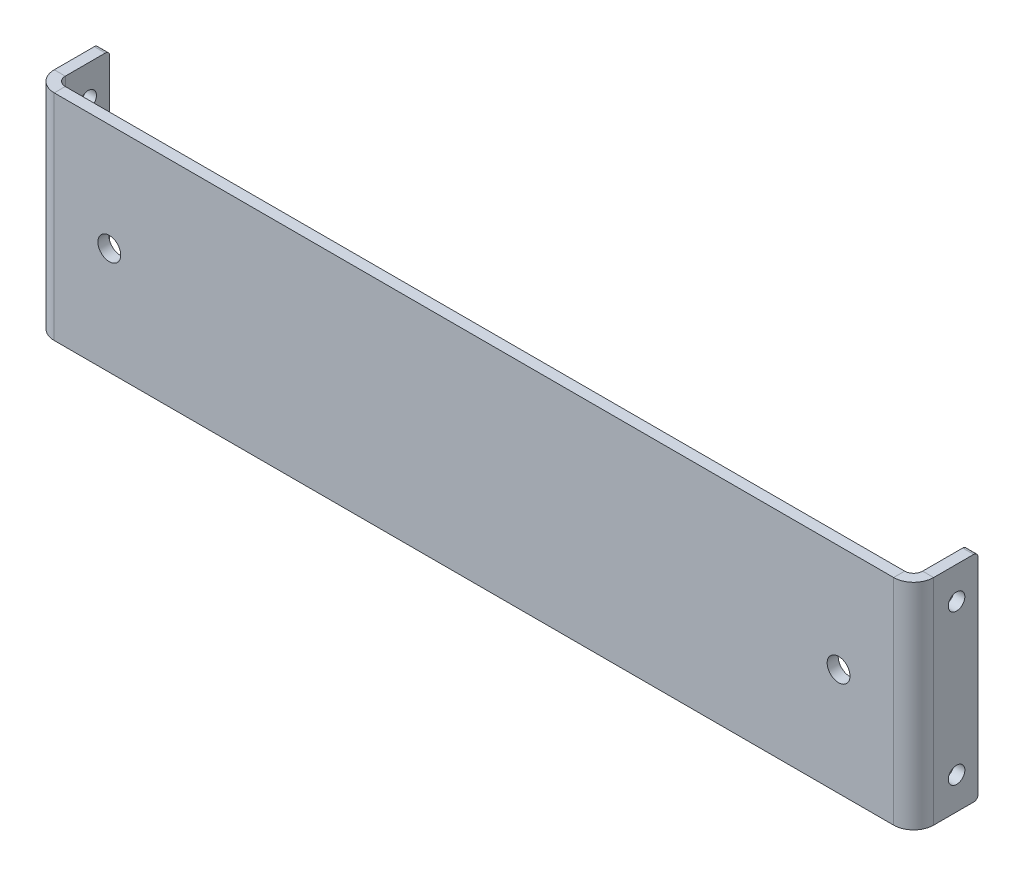
SolidWorks part; units mm, degrees
note: The reader was unsure of these and kept them because the rebuilt part matched: flange length of "Edge-Flange1".
ref_plane "Front Plane" through (0, 0, 0) normal (0, 0, 1) x (1, 0, 0)
ref_plane "Top Plane" through (0, 0, 0) normal (0, 1, 0) x (1, 0, 0)
ref_plane "Right Plane" through (0, 0, 0) normal (1, 0, 0) x (0, 0, -1)
sketch "Sketch1" plane through (0, 0, 0) normal (0, 0, 1) x (1, 0, 0)
  line L1 (-130.175, -31.75) -> (130.175, -31.75)
  line L2 (-130.175, -31.75) -> (-130.175, 31.75)
  line L3 (-130.175, 31.75) -> (130.175, 31.75)
  line L4 (130.175, -31.75) -> (130.175, 31.75)
  line L5 (-130.175, -31.75) -> (130.175, 31.75) construction
  line L6 (-130.175, 31.75) -> (130.175, -31.75) construction
  point P0 (0, 0)
  dimension "D1" = 260.35
  dimension "D2" = 63.5
base flange "Base-Flange1" sketch "Sketch1" thickness 3.2639 reverse thickness direction no parameters "D1"=2.6568
edge flange "Edge-Flange1" sketch "Sketch10" flange profiles "Sketch10", "Sketch11" flange angle 90 flange length 19.05 flange position material inside bend radius 2.6568 thickness 3.2639 relief rectangular parameters "D6"=10, "D8"=1
sketch "Sketch10" plane through (130.175, 0, -3.2639) normal (-1, 0, 0) x (0, 1, 0)
  line L2 (-31.75, 0) -> (-31.75, 15.7861)
  line L3 (-31.75, 15.7861) -> (31.75, 15.7861)
  line L4 (31.75, 15.7861) -> (31.75, 0)
  line L5 (31.75, 0) -> (-31.75, 0) construction
  line L6 (31.75, 0) -> (-31.75, 0)
sketch "Sketch11" plane through (-130.175, 0, -3.2639) normal (1, 0, 0) x (0, -1, 0)
  line L0 (31.75, 0) -> (-31.75, 0) construction
  line L1 (31.75, 0) -> (-31.75, 0)
  line L2 (31.75, 0) -> (31.75, 15.7861)
  line L3 (31.75, 15.7861) -> (-31.75, 15.7861)
  line L4 (-31.75, 15.7861) -> (-31.75, 0)
bend "EdgeBend1" bend radius 2.6568 bend angle 90 parameters "D5"=1
bend "EdgeBend2" bend radius 2.6568 bend angle 90 parameters "D5"=2
hole_wizard "#10 (0.1935) Diameter Hole1" positions "Sketch12" profile "Sketch13" hole size "#10" standard "ANSI Inch" end condition through all
sketch "Sketch12" plane through (130.175, 0, 0) normal (1, 0, 0) x (0, 0, -1)
  line L0 (0, -31.75) -> (0, 31.75) construction
  line L1 (5.9207, 31.75) -> (19.05, 31.75) construction
  line L2 (19.05, -31.75) -> (5.9207, -31.75) construction
  point P0 (12.7, 22.225)
  point P2 (12.7, -22.225)
  dimension "D1" = 12.7
  dimension "D2" = 9.525
  dimension "D3" = 9.525
sketch "Sketch13" plane through (130.175, 22.225, -12.7) normal (0, 1, 0) x (0, 0, -1)
  line L0 (0, 0) -> (0, 260.35)
  line L1 (0, 260.35) -> (2.4574, 260.35)
  line L2 (2.4574, 260.35) -> (2.4574, 0)
  line L5 (2.4574, 0) -> (0, 0)
  line L11 (0, -6.35) -> (0, 107.95) construction
  dimension "Thru Hole Dia." = 4.9149
  dimension "Thru Hole Depth" = 260.35
fillet "Fillet1" radius 1.27 4 edges at (-128.5431, 31.75, -19.05) (-128.5431, -31.75, -19.05) (128.5431, -31.75, -19.05) (128.5431, 31.75, -19.05)
hole_wizard "1/4 Clearance Hole1" positions "Sketch14" profile "Sketch15" hole size "1/4" standard "ANSI Inch" end condition through all
sketch "Sketch14" plane through (0, 0, 0) normal (0, 0, 1) x (1, 0, 0)
  line L0 (-124.2543, -31.75) -> (124.2543, -31.75) construction
  point P0 (-107.95, 0)
  point P2 (107.95, 0)
  dimension "D1" = 107.95
  dimension "D2" = 215.9
  dimension "D3" = 31.75
sketch "Sketch15" plane through (-107.95, 0, 0) normal (1, 0, 0) x (0, -1, 0)
  line L0 (0, 0) -> (0, 19.05)
  line L1 (0, 19.05) -> (3.3782, 19.05)
  line L2 (3.3782, 19.05) -> (3.3782, 0)
  line L5 (3.3782, 0) -> (0, 0)
  line L11 (0, -6.35) -> (0, 107.95) construction
  dimension "Thru Hole Dia." = 6.7564
  dimension "Thru Hole Depth" = 19.05
sketch "Bend-Lines1" [suppressed] plane through (0, 0, 0) normal (0, 1, 0) x (1, 0, 0)
sketch "Bounding-Box1" [suppressed] plane through (0, 0, 0) normal (0, 1, 0) x (1, 0, 0)
sheet metal parameters "Sheet-Metal1" thickness 3.2639 parameters "D1"=2.6568
flat pattern "Flat-Pattern1" [suppressed]
sketch "Bend-Lines2" plane through (0, 0, 0) normal (0, 1, 0) x (1, 0, 0)
sketch3d "Bounding-Box2" [suppressed]
  line L0 (130.175, -38.1, 0) -> (-130.175, -38.1, 0) construction
  line L1 (130.175, 38.1, 0) -> (-130.175, 38.1, 0) construction
  line L2 (130.175, -38.1, 0) -> (130.175, 38.1, 0) construction
  line L3 (-130.175, -38.1, 0) -> (-130.175, 38.1, 0) construction
sheet metal parameters "Sheet-Metal2" thickness 3.2639 parameters "D1"=2.6568
flat pattern "Flat-Pattern1"
sketch "Bend-Lines2" plane through (0, 0, 0) normal (0, 0, 1) x (1, 0, 0)
  line L0 (-127.6227, 38.1) -> (-127.6227, -38.1) construction
  line L1 (127.6227, -38.1) -> (127.6227, 38.1) construction
  line L2 (-127.6227, 38.1) -> (-127.6227, -38.1) construction
  line L3 (127.6227, -38.1) -> (127.6227, 38.1) construction
sketch3d "Bounding-Box2" [suppressed]
  line L0 (-144.1203, -38.1, 0) -> (144.1203, -38.1, 0) construction
  line L1 (-144.1203, 38.1, 0) -> (144.1203, 38.1, 0) construction
  line L2 (-144.1203, -38.1, 0) -> (-144.1203, 38.1, 0) construction
  line L3 (144.1203, -38.1, 0) -> (144.1203, 38.1, 0) construction
bend of the flat pattern "Flatten-<EdgeBend1>1"
bend of the flat pattern "Flatten-<EdgeBend2>1"
sheet metal parameters "Sheet-Metal3" thickness 3.2639 parameters "D1"=2.6568
flat pattern "Flat-Pattern1"
sketch "Bend-Lines2" plane through (0, 0, 0) normal (0, 0, 1) x (1, 0, 0)
  line L0 (-127.6227, 38.1) -> (-127.6227, -38.1) construction
  line L1 (127.6227, -38.1) -> (127.6227, 38.1) construction
  line L2 (-127.6227, 38.1) -> (-127.6227, -38.1) construction
  line L3 (127.6227, -38.1) -> (127.6227, 38.1) construction
sketch3d "Bounding-Box2" [suppressed]
  line L0 (-144.1203, -38.1, 0) -> (144.1203, -38.1, 0) construction
  line L1 (-144.1203, 38.1, 0) -> (144.1203, 38.1, 0) construction
  line L2 (-144.1203, -38.1, 0) -> (-144.1203, 38.1, 0) construction
  line L3 (144.1203, -38.1, 0) -> (144.1203, 38.1, 0) construction
bend of the flat pattern "Flatten-<EdgeBend1>1"
bend of the flat pattern "Flatten-<EdgeBend2>1"
sheet metal parameters "Sheet-Metal4" thickness 3.2639 parameters "D1"=2.6568
flat pattern "Flat-Pattern1"
sketch "Bend-Lines2" plane through (0, 0, 0) normal (0, 0, 1) x (1, 0, 0)
  line L0 (-127.6227, 31.75) -> (-127.6227, -31.75) construction
  line L1 (127.6227, -31.75) -> (127.6227, 31.75) construction
  line L2 (-127.6227, 31.75) -> (-127.6227, -31.75) construction
  line L3 (127.6227, -31.75) -> (127.6227, 31.75) construction
sketch3d "Bounding-Box2" [suppressed]
  line L0 (-144.1203, -31.75, 0) -> (144.1203, -31.75, 0) construction
  line L1 (-144.1203, 31.75, 0) -> (144.1203, 31.75, 0) construction
  line L2 (-144.1203, -31.75, 0) -> (-144.1203, 31.75, 0) construction
  line L3 (144.1203, -31.75, 0) -> (144.1203, 31.75, 0) construction
bend of the flat pattern "Flatten-<EdgeBend1>1"
bend of the flat pattern "Flatten-<EdgeBend2>1"
